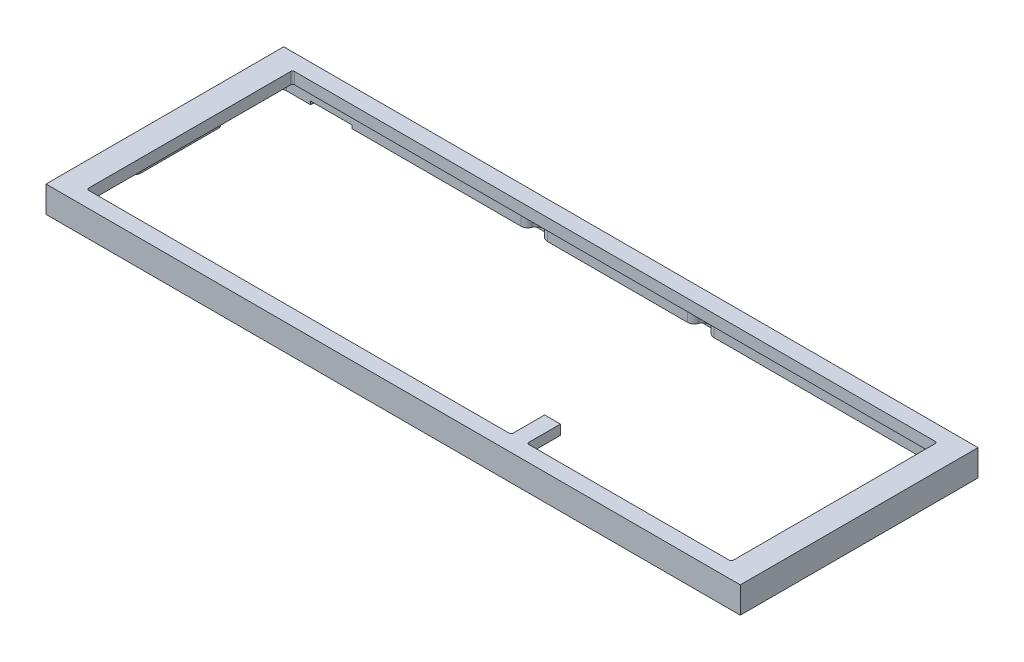
SolidWorks part; units mm, degrees
material "6061 Alloy"
ref_plane "Front Plane" through (0, 0, 0) normal (0, 0, 1) x (1, 0, 0)
ref_plane "Top Plane" through (0, 0, 0) normal (0, 1, 0) x (1, 0, 0)
ref_plane "Right Plane" through (0, 0, 0) normal (1, 0, 0) x (0, 0, -1)
sketch "Sketch1" plane through (0, 0, 0) normal (0, 1, 0) x (1, 0, 0)
  line L1 (0, 0) -> (390.8, 0)
  line L2 (0, 0) -> (0, -133.8)
  line L3 (0, -133.8) -> (390.8, -133.8)
  line L4 (390.8, 0) -> (390.8, -133.8)
  dimension "D1" = 390.8
  dimension "D2" = 133.8
extrude "Boss-Extrude1" add sketch "Sketch1" along normal blind 13.1
sketch "Sketch2" plane through (0, 13.1, 0) normal (0, 1, 0) x (1, 0, 0)
  line L0 (390.8, 0) -> (0, 0) construction
  line L1 (14, -9) -> (376.8, -9)
  line L2 (14, -9) -> (14, -124.9)
  line L3 (14, -124.9) -> (376.8, -124.9)
  line L4 (376.8, -9) -> (376.8, -124.9)
  line L5 (0, -133.8) -> (390.8, -133.8) construction
  line L6 (0, 0) -> (0, -133.8) construction
  line L7 (390.8, -133.8) -> (390.8, 0) construction
  line L8 (390.8, -133.8) -> (390.8, 0) construction
  line L9 (261.8, -124.9) -> (252.9, -124.9)
  line L10 (261.8, -124.9) -> (261.8, -106.05)
  line L11 (261.8, -106.05) -> (252.9, -106.05)
  line L12 (252.9, -124.9) -> (252.9, -106.05)
  line L13 (0, -133.8) -> (390.8, -133.8) construction
  dimension "D1" = 9
  dimension "D2" = 8.9
  dimension "D3" = 14
  dimension "D4" = 14
  dimension "D5" = 129
  dimension "D6" = 137.9
  dimension "D7" = 27.75
extrude "Cut-Extrude1" cut sketch "Sketch2" against normal through all contours L3 L12 L11 L10 L4 L1 L2 region at (195.1518, 13.1, 66.7556)
sketch "Sketch3" plane through (0, 0, 0) normal (0, -1, 0) x (1, 0, 0)
  line L0 (390.8, 0) -> (0, 0) construction
  line L1 (385.5, 2.6) -> (5.3, 2.6)
  line L2 (385.5, 2.6) -> (385.5, 131.2)
  line L3 (385.5, 131.2) -> (5.3, 131.2)
  line L4 (5.3, 2.6) -> (5.3, 131.2)
  line L5 (390.8, 133.8) -> (390.8, 0) construction
  point P4 (195.4, 2.6)
  point P7 (195.4, 0)
  point P8 (385.5, 66.9)
  point P11 (390.8, 66.9)
  dimension "D1" = 380.2
  dimension "D2" = 128.6
extrude "Cut-Extrude2" cut sketch "Sketch3" against normal blind 6.6 contours L2 L1 L4 L3
sketch "Sketch5" plane through (0, 6.6, 0) normal (0, -1, 0) x (1, 0, 0)
  line L0 (290, 128.2) -> (285, 128.2)
  line L1 (290, 128.2) -> (290, 131.2)
  line L2 (290, 131.2) -> (285, 131.2)
  line L3 (285, 128.2) -> (285, 131.2)
  line L4 (105, 128.2) -> (100, 128.2)
  line L5 (105, 128.2) -> (105, 131.2)
  line L6 (105, 131.2) -> (100, 131.2)
  line L7 (100, 128.2) -> (100, 131.2)
  line L8 (8.3, 45) -> (8.3, 88.8)
  line L9 (382.5, 45) -> (382.5, 88.8)
  line L10 (0, 133.8) -> (390.8, 133.8) construction
  line L11 (5.3, 2.6) -> (5.3, 131.2) construction
  line L12 (390.8, 0) -> (0, 0) construction
  line L13 (385.5, 2.6) -> (385.5, 131.2) construction
  line L15 (385.5, 131.2) -> (5.3, 131.2) construction
  line L16 (385.5, 131.2) -> (5.3, 131.2) construction
  line L17 (385.5, 2.6) -> (5.3, 2.6) construction
  line L18 (5.3, 2.6) -> (5.3, 131.2) construction
  circle A0 centre (102.5, 128.2) radius 2.5
  circle A1 centre (287.5, 128.2) radius 2.5
  circle A2 centre (102.5, 2.6) radius 2.5
  circle A3 centre (195.4, 2.6) radius 2.5
  circle A4 centre (287.5, 2.6) radius 2.5
  circle A5 centre (385.5, 45) radius 3
  circle A6 centre (385.5, 88.8) radius 3
  circle A7 centre (5.3, 45) radius 3
  circle A8 centre (5.3, 88.8) radius 3
  line M9 (5.3, 131.2) -> (5.3, 2.6)
  line M10 (5.3, 2.6) -> (385.5, 2.6)
  line M11 (385.5, 2.6) -> (385.5, 131.2)
  dimension "D1" = 5
  dimension "D5" = 6
  dimension "D2" = 185
  dimension "D3" = 92.9
  dimension "D4" = 185
  dimension "D6" = 45
  dimension "D7" = 97.2
  dimension "D8" = 3
  dimension "D9" = 97.2
  dimension "D10" = 45
  dimension "D11" = 45
extrude "Boss-Extrude2" add sketch "Sketch5" along normal up to surface (6.6 mm away) contours A6 L9 A5 M11 | A5 M11 | A6 M11 | A4 M10 | A3 M10 | A2 M10 | A7 M9 | A8 A7 L8 M9 | A8 M9 | A0 | L7 L6 L5 L4 | L3 L2 L1 L0 | A1 region at (6.8273, 6.6, 66.9) region at (6.5732, 6.6, 45) region at (384.2268, 6.6, 45) region at (287.5, 6.6, 3.661) region at (195.4, 6.6, 3.661) region at (102.5, 6.6, 3.661) region at (6.5732, 6.6, 88.8) region at (383.9727, 6.6, 66.9) region at (384.2268, 6.6, 88.8) up to face at (195.4, 0, 66.9)
sketch "Sketch6" plane through (0, 6.6, 0) normal (0, -1, 0) x (-1, 0, 0)
  line L0 (-195.4, 0) -> (-195.4, -133.8) construction
  line L1 (-390.8, 0) -> (0, 0) construction
  line L2 (0, -133.8) -> (-390.8, -133.8) construction
  line L3 (-390.8, -66.9) -> (0, -66.9) construction
  line L4 (-390.8, -133.8) -> (-390.8, 0) construction
  line L5 (0, 0) -> (0, -133.8) construction
  line L6 (-285, -2.6) -> (-197.9, -2.6) construction
  line L7 (-385.5, -2.6) -> (-385.5, -42) construction
  line L8 (-385.5, -2.6) -> (-385.5, -42) construction
  point P12 (-382.9, -22.7)
  point P13 (-382.9, -111)
  point P14 (-324.8, -129)
  point P15 (-192.2, -129)
  point P16 (-148.6, -5.4)
  point P18 (-64.4, -129)
  point P19 (-7.9, -111)
  point P20 (-7.9, -22.7)
  point P22 (-242.3, -5.4)
  dimension "D1" = 22.8
  dimension "D2" = 22.7
  dimension "D3" = 7.9
  dimension "D4" = 66
  dimension "D5" = 4.8
  dimension "D6" = 198.6
  dimension "D7" = 326.4
  dimension "D8" = 2.8
  dimension "D9" = 143.2
  dimension "D10" = 236.9
sketch "Sketch7" plane through (0, 0, 0) normal (0, -1, 0) x (1, 0, 0)
  arc A0 (382.5, 45) -> (385.5, 42) centre (385.5, 45) ccw construction
  arc A1 (385.5, 91.8) -> (382.5, 88.8) centre (385.5, 88.8) ccw construction
  arc A2 (290, 2.6) -> (285, 2.6) centre (287.5, 2.6) ccw construction
  arc A3 (197.9, 2.6) -> (192.9, 2.6) centre (195.4, 2.6) ccw construction
  arc A4 (105, 2.6) -> (100, 2.6) centre (102.5, 2.6) ccw construction
  arc A5 (5.3, 42) -> (8.3, 45) centre (5.3, 45) ccw construction
  arc A6 (8.3, 88.8) -> (5.3, 91.8) centre (5.3, 88.8) ccw construction
  arc A7 (100, 128.2) -> (105, 128.2) centre (102.5, 128.2) ccw construction
  arc A8 (285, 128.2) -> (290, 128.2) centre (287.5, 128.2) ccw construction
  point P0 (385.5, 45)
  point P1 (385.5, 88.8)
  point P2 (287.5, 128.2)
  point P3 (102.5, 128.2)
  point P4 (5.3, 88.8)
  point P5 (5.3, 45)
  point P6 (102.5, 2.6)
  point P7 (195.4, 2.6)
  point P8 (287.5, 2.6)
sketch "Sketch8" plane through (0, 6.6, 0) normal (0, -1, 0) x (1, 0, 0)
  line L1 (261.8, 106.05) -> (252.9, 106.05)
  line L2 (261.8, 106.05) -> (261.8, 124.9)
  line L3 (261.8, 124.9) -> (252.9, 124.9)
  line L4 (252.9, 106.05) -> (252.9, 124.9)
extrude "Cut-Extrude3" cut sketch "Sketch8" against normal blind 1
hole_wizard "M2x0.4 Tapped Hole2" positions "3DSketch3" profile "Sketch11" tap size "M2x0.4" standard "ANSI Metric"
sketch3d "3DSketch3"
  point P0 (382.9, 6.6, 22.7)
  point P3 (382.9, 6.6, 111)
  point P6 (324.8, 6.6, 129)
  point P9 (192.2, 6.6, 129)
  point P12 (64.4, 6.6, 129)
  point P15 (7.9, 6.6, 22.7)
  point P18 (7.9, 6.6, 111)
  point P22 (242.3, 6.6, 5.4)
  point P25 (148.6, 6.6, 5.4)
sketch "Sketch11" plane through (382.9, 6.6, 22.7) normal (1, 0, 0) x (0, 0, -1)
  line L0 (0, 0) -> (0, 4.4807)
  line L1 (0, 4.4807) -> (0.8, 4)
  line L2 (0.8, 4) -> (0.8, 0)
  line L5 (0.8, 0) -> (0, 0)
  line L10 (0, 4.4807) -> (-0.8, 4) construction
  line L11 (0, -6.35) -> (0, 107.95) construction
  dimension "Tap Drill Dia." = 1.6
  dimension "Tap Drill Depth" = 4
  dimension "Drill Angle" = 118
cosmetic thread "Hole Thread10" parameters "D1"=4, "D2"=2
cosmetic thread "Hole Thread11" parameters "D1"=4, "D2"=2
cosmetic thread "Hole Thread12" parameters "D1"=4, "D2"=2
cosmetic thread "Hole Thread13" parameters "D1"=4, "D2"=2
cosmetic thread "Hole Thread14" parameters "D1"=4, "D2"=2
cosmetic thread "Hole Thread15" parameters "D1"=4, "D2"=2
cosmetic thread "Hole Thread16" parameters "D1"=4, "D2"=2
cosmetic thread "Hole Thread17" parameters "D1"=4, "D2"=2
cosmetic thread "Hole Thread18" parameters "D1"=4, "D2"=2
fillet "Fillet1" radius 4 12 edges at (385.5, 3.3, 42) (385.5, 3.3, 2.6) (5.3, 3.3, 2.6) (5.3, 3.3, 42) (5.3, 3.3, 91.8) (5.3, 3.3, 131.2) (100, 3.3, 131.2) (105, 3.3, 131.2) (290, 3.3, 131.2) (285, 3.3, 131.2) (385.5, 3.3, 131.2) (385.5, 3.3, 91.8)
fillet "Fillet2" radius 1.1 12 edges at (376.8, 9.85, 9) (376.8, 9.85, 124.9) (14, 9.85, 124.9) (14, 9.85, 9) (105, 3.3, 2.6) (100, 3.3, 2.6) (197.9, 3.3, 2.6) (192.9, 3.3, 2.6) (285, 3.3, 2.6) (290, 3.3, 2.6) (261.8, 10.35, 124.9) (252.9, 10.35, 124.9)
sketch "Sketch14" plane through (0, 0, 0) normal (0, -1, 0) x (1, 0, 0)
  line L0 (390.8, 0) -> (0, 0) construction
  line L1 (388.8, 0) -> (2, 0)
  line L2 (388.8, 0) -> (388.8, 131.8)
  line L3 (388.8, 131.8) -> (2, 131.8)
  line L4 (2, 0) -> (2, 131.8)
  line L5 (0, 0) -> (0, 133.8) construction
  line L6 (390.8, 133.8) -> (390.8, 0) construction
  line L7 (0, 133.8) -> (390.8, 133.8) construction
  line L9 (390.8, 0) -> (0, 0)
  line L10 (390.8, 0) -> (390.8, 133.8)
  line L11 (390.8, 133.8) -> (0, 133.8)
  line L12 (0, 0) -> (0, 133.8)
  line L13 (390.8, 0) -> (0, 0)
  line L14 (390.8, 0) -> (390.8, 2)
  line L15 (390.8, 2) -> (0, 2)
  line L16 (0, 0) -> (0, 2)
  line M21 (0, 0) -> (390.8, 0)
  line M22 (390.8, 0) -> (390.8, 133.8)
  line M25 (0, 0) -> (390.8, 0)
  dimension "D1" = 2
  dimension "D2" = 2
  dimension "D3" = 2
  dimension "D4" = 2
extrude "Boss-Extrude3" add sketch "Sketch14" along normal blind 1.7 contours L12 L9 L4 L3 L2 L10 L11 | L2 L15 L4 M25 M21 | L15 L2 M22 M21 | L4 L15 L12 M25 region at (195.4, 0, 1) region at (389.8, 0, 1) region at (1, 0, 1) region at (389.2124, 0, 66.9)
sketch "Sketch16" plane through (0, 6.6, 0) normal (0, -1, 0) x (1, 0, 0)
  line L0 (5.3, 6.6) -> (5.3, 39.2554) construction
  line L1 (385.5, 2.6) -> (5.3, 2.6)
  line L2 (385.5, 2.6) -> (385.5, 7.6)
  line L3 (385.5, 7.6) -> (5.3, 7.6)
  line L4 (5.3, 2.6) -> (5.3, 7.6)
  line L5 (385.5, 6.6) -> (385.5, 39.2554) construction
  line L6 (381.5, 2.6) -> (290.9278, 2.6) construction
  line L7 (246.3, 6.4) -> (246.3, 7.6)
  line L8 (238.3, 6.4) -> (238.3, 7.6)
  line L9 (152.6, 6.4) -> (152.6, 7.6)
  line L10 (144.6, 6.4) -> (144.6, 7.6)
  circle A0 centre (242.3, 6.4) radius 4
  circle A1 centre (148.6, 6.4) radius 4
  point P24 (242.3, 5.4)
  point P25 (0, 0)
  point P26 (148.6, 5.4)
  dimension "D2" = 8
  dimension "D1" = 5
  dimension "D3" = 1.2
  dimension "D4" = 1.2
extrude "Boss-Extrude4" add sketch "Sketch16" along normal up to surface (6.6 mm away) contours A0 L1 L2 L3 L7 | A1 L1 A0 L8 L3 L9 | A1 L10 L3 L4 L1 region at (315.6181, 6.6, 5.0935) region at (195.45, 6.6, 5.079) region at (75.2319, 6.6, 5.0935) up to face at (195.4, 0, 66.9)
sketch "Sketch17" plane through (0, 6.6, 0) normal (0, -1, 0) x (1, 0, 0)
  circle A0 centre (148.6, 5.4) radius 3
  circle A1 centre (242.3, 5.4) radius 3
extrude "Cut-Extrude5" cut sketch "Sketch17" along normal up to surface (6.6 mm away) up to face at (195.3316, 0, 64.1007)
sketch "Sketch18" plane through (0, 0, 0) normal (0, 0, -1) x (-1, 0, 0)
  line L0 (0, -1.7) -> (-390.8, -1.7) construction
  line L1 (-40.3, -1.7) -> (-28.3, -1.7)
  line L2 (-40.3, -1.7) -> (-40.3, 1.8)
  line L3 (-40.3, 1.8) -> (-28.3, 1.8)
  line L4 (-28.3, -1.7) -> (-28.3, 1.8)
  line L5 (0, 13.1) -> (0, -1.7) construction
  point P6 (-34.3, 1.8)
  dimension "D1" = 12
  dimension "D2" = 3.5
  dimension "D3" = 34.3
extrude "Cut-Extrude6" cut sketch "Sketch18" against normal blind 10
fillet "Fillet4" radius 4 4 edges at (144.6, 3.3, 7.6) (152.6, 3.3, 7.6) (238.3, 3.3, 7.6) (246.3, 3.3, 7.6)
hole_wizard "M2x0.4 Tapped Hole3" positions "3DSketch2" profile "Sketch10" tap size "M2x0.4" standard "ANSI Metric"
sketch3d "3DSketch2"
  line L0 (390.8, -1.7, 0) -> (390.8, -1.7, 133.8) construction
  line L1 (0, -1.7, 133.8) -> (0, -1.7, 0) construction
  line L7 (388.8, 0, 2) -> (40.3, 0, 2) construction
  point P0 (385.5, 0, 45)
  point P3 (385.5, 0, 88.8)
  point P6 (287.5, 0, 128.2)
  point P9 (102.5, 0, 128.2)
  point P12 (5.3, 0, 88.8)
  point P15 (5.3, 0, 45)
  point P30 (312.8185, 0, 4.3)
  point P32 (195.4074, 0, 4.3)
  point P34 (77.9815, 0, 4.3)
  dimension "D1" = 78
  dimension "D2" = 78
  dimension "D3" = 195.4
  dimension "D4" = 2.3
sketch "Sketch10" plane through (385.5, 0, 45) normal (1, 0, 0) x (0, 0, -1)
  line L0 (0, 0) -> (0, 4.4807)
  line L1 (0, 4.4807) -> (0.8, 4)
  line L2 (0.8, 4) -> (0.8, 0)
  line L5 (0.8, 0) -> (0, 0)
  line L10 (0, 4.4807) -> (-0.8, 4) construction
  line L11 (0, -6.35) -> (0, 107.95) construction
  dimension "Tap Drill Dia." = 1.6
  dimension "Tap Drill Depth" = 4
  dimension "Drill Angle" = 118
cosmetic thread "Hole Thread4" parameters "D1"=4, "D2"=2
cosmetic thread "Hole Thread5" parameters "D1"=4, "D2"=2
cosmetic thread "Hole Thread6" parameters "D1"=4, "D2"=2
cosmetic thread "Hole Thread7" parameters "D1"=4, "D2"=2
cosmetic thread "Hole Thread8" parameters "D1"=4, "D2"=2
cosmetic thread "Hole Thread9" parameters "D1"=4, "D2"=2
cosmetic thread "Hole Thread19" parameters "D1"=4, "D2"=2
cosmetic thread "Hole Thread20" parameters "D1"=4, "D2"=2
cosmetic thread "Hole Thread21" parameters "D1"=4, "D2"=2
fillet "Fillet5" radius 4 6 edges at (5.3, 3.3, 7.6) (385.5, 3.3, 7.6) (388.8, -0.85, 2) (388.8, -0.85, 131.8) (2, -0.85, 131.8) (2, -0.85, 2)
sketch "Sketch20" plane through (0, 0, 0) normal (0, -1, 0) x (1, 0, 0)
  line L2 (40.3, 2) -> (40.3, 7.6)
  line L3 (40.3, 7.6) -> (45.9, 7.6)
  line L4 (28.3, 2) -> (28.3, 7.6)
  line L5 (28.3, 7.6) -> (22.7, 7.6)
  line L6 (384.8, 2) -> (40.3, 2) construction
  circle A0 centre (40.3, 7.6) radius 5.6
  circle A1 centre (28.3, 7.6) radius 5.6
extrude "Cut-Extrude7" cut sketch "Sketch20" against normal up to surface (1.8 mm away) contours L2 A0 L3 | L5 A1 L4 region at (42.6767, 0, 5.2233) region at (25.9233, 0, 5.2233) up to face at (34.3, 1.8, 3.8)
